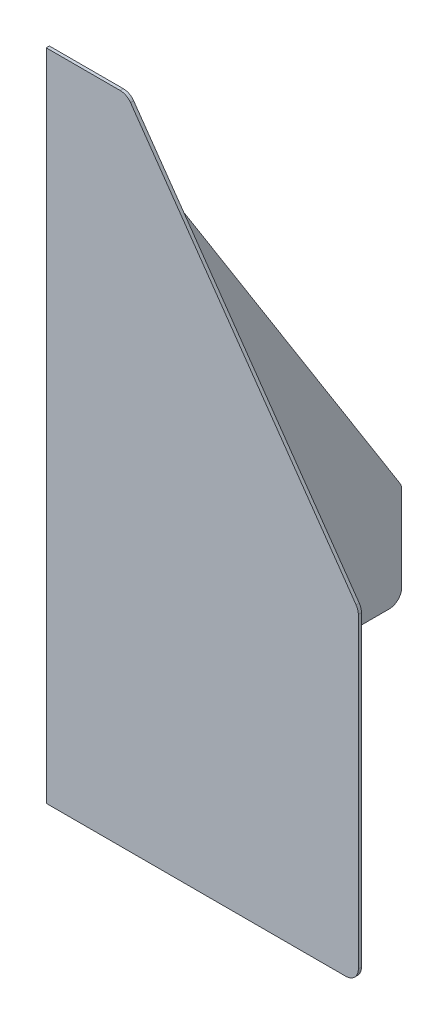
SolidWorks part; units mm, degrees
ref_plane "Front Plane" through (0, 0, 0) normal (0, 0, 1) x (1, 0, 0)
ref_plane "Top Plane" through (0, 0, 0) normal (0, 1, 0) x (1, 0, 0)
ref_plane "Right Plane" through (0, 0, 0) normal (1, 0, 0) x (0, 0, -1)
sketch "Sketch1" plane through (0, 0, 0) normal (0, 1, 0) x (1, 0, 0)
  line L0 (0, 0) -> (0, 177.8)
  line L1 (0, 177.8) -> (1.5875, 177.8)
  line L2 (1.5875, 177.8) -> (1.5875, 1.5875)
  line L3 (1.5875, 1.5875) -> (157.48, 1.5875)
  line L4 (157.48, 1.5875) -> (157.48, 0)
  line L5 (157.48, 0) -> (0, 0)
  dimension "D1" = 157.48
  dimension "D2" = 177.8
  dimension "D3" = 1.5875
  dimension "D4" = 1.5875
extrude "Boss-Extrude1" add sketch "Sketch1" along normal blind 330.2
sketch "Sketch2" plane through (0, 0, 0) normal (-1, 0, 0) x (0, 0, 1)
  line L0 (-177.8, 50.8) -> (-1.5875, 330.2)
  line L1 (-1.5875, 330.2) -> (-177.8, 330.2)
  line L2 (-177.8, 330.2) -> (-177.8, 50.8)
  line L3 (0, 330.2) -> (0, 0) construction
  line L4 (-177.8, 330.2) -> (-177.8, 0) construction
  line L5 (-177.8, 330.2) -> (0, 330.2) construction
  dimension "D1" = 1.5875
  dimension "D2" = 50.8
extrude "Cut-Extrude1" cut sketch "Sketch2" against normal up to surface (1.5875 mm away) up to face at (1.5875, 165.1, -89.6937)
sketch "Sketch3" plane through (0, 0, 0) normal (0, 0, 1) x (1, 0, 0)
  line L0 (40.64, 330.2) -> (157.48, 330.2)
  line L1 (157.48, 330.2) -> (157.48, 163.322)
  line L2 (157.48, 163.322) -> (40.64, 330.2)
  line L3 (0, 0) -> (157.48, 0) construction
  line L4 (157.48, 330.2) -> (157.48, 0) construction
  line L5 (0, 330.2) -> (157.48, 330.2) construction
  line L6 (0, 330.2) -> (0, 0) construction
  dimension "D1" = 163.322
  dimension "D2" = 40.64
extrude "Cut-Extrude2" cut sketch "Sketch3" against normal up to surface (1.5875 mm away) up to face at (79.5337, 165.1, -1.5875)
fillet "Fillet2" radius 6.35 6 edges at (0.7937, 0, -177.8) (0.7937, 50.8, -177.8) (40.64, 330.2, -0.7937) (157.48, 0, -0.7937) (157.48, 163.322, -0.7937) (1.5875, 165.1, -1.5875)
